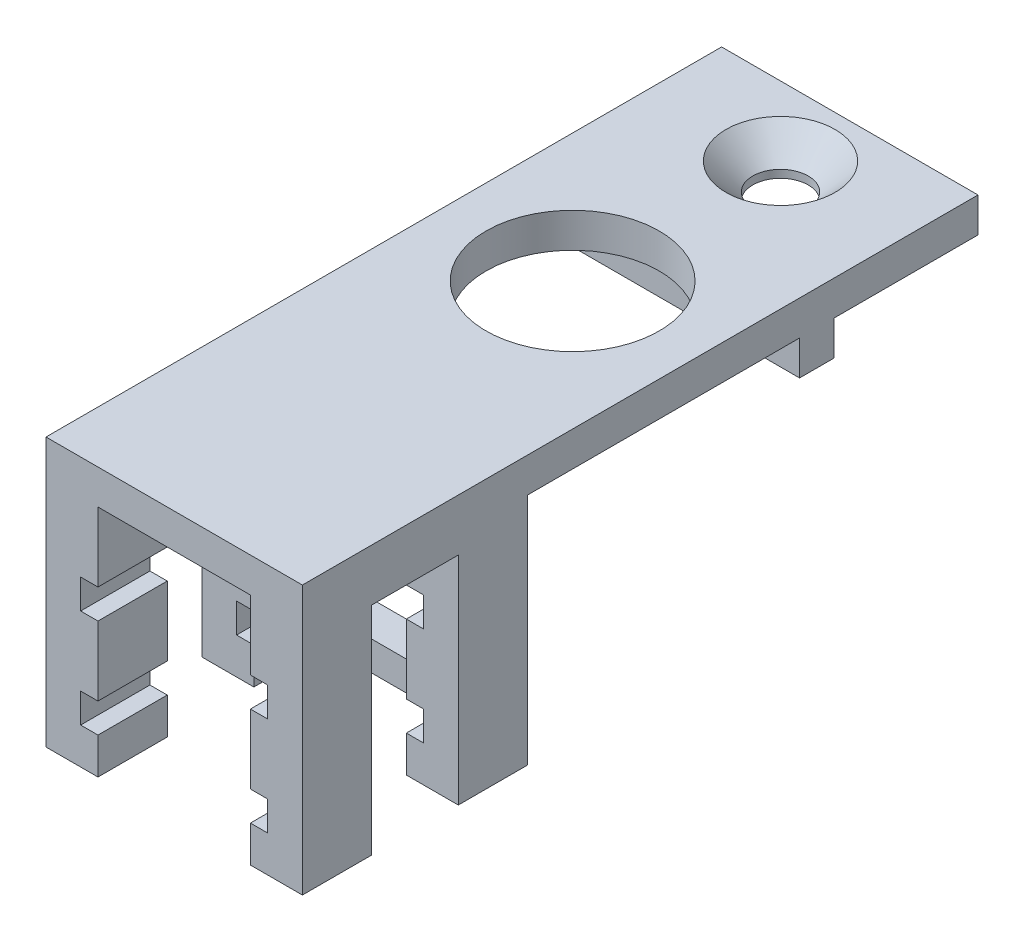
SolidWorks part; units mm, degrees
ref_plane "Front Plane" through (0, 0, 0) normal (0, 0, 1) x (1, 0, 0)
ref_plane "Top Plane" through (0, 0, 0) normal (0, 1, 0) x (1, 0, 0)
ref_plane "Right Plane" through (0, 0, 0) normal (1, 0, 0) x (0, 0, -1)
sketch "Sketch1" plane through (0, 0, 0) normal (0, 1, 0) x (1, 0, 0)
  line L5 (-6.5, -7.4) -> (6.5, -7.4)
  line L6 (-6.5, -7.4) -> (-6.5, 7.4)
  line L7 (-6.5, 7.4) -> (6.5, 7.4)
  line L8 (6.5, -7.4) -> (6.5, 7.4)
  line L9 (-6.5, -7.4) -> (6.5, 7.4) construction
  line L10 (-6.5, 7.4) -> (6.5, -7.4) construction
  point P0 (0, 0)
  dimension "D1" = 14.8
  dimension "D2" = 13
extrude "Boss-Extrude1" add sketch "Sketch1" along normal blind 15.5
sketch "Sketch2" plane through (6.5, 0, 0) normal (1, 0, 0) x (0, 0, -1)
  line L0 (-7.4, 0) -> (7.4, 0) construction
  line L1 (-5.4, 0) -> (5.4, 0)
  line L2 (-5.4, 0) -> (-5.4, 13.5)
  line L3 (-5.4, 13.5) -> (5.4, 13.5)
  line L4 (5.4, 0) -> (5.4, 13.5)
  line L5 (-7.4, 15.5) -> (7.4, 15.5) construction
  line L6 (-7.4, 15.5) -> (-7.4, 0) construction
  line L7 (7.4, 15.5) -> (7.4, 0) construction
  dimension "D1" = 2
  dimension "D2" = 2
  dimension "D3" = 2
extrude "Cut-Extrude1" cut sketch "Sketch2" against normal offset from surface (11 mm away) 2 up to face at (-6.5, 7.75, 0)
sketch "Sketch3" plane through (6.5, 0, 0) normal (1, 0, 0) x (0, 0, -1)
  line L0 (-7.4, 15.5) -> (-7.4, 0) construction
  line L1 (-7.4, 2.1) -> (-4.4, 2.1)
  line L2 (-7.4, 2.1) -> (-7.4, 0)
  line L3 (-7.4, 0) -> (-4.4, 0)
  line L4 (-4.4, 2.1) -> (-4.4, 0)
  line L7 (-7.4, 3.8) -> (-4.4, 3.8)
  line L8 (-7.4, 3.8) -> (-7.4, 7.8)
  line L9 (-7.4, 7.8) -> (-4.4, 7.8)
  line L10 (-4.4, 3.8) -> (-4.4, 7.8)
  line L11 (-7.4, 13.5) -> (-4.4, 13.5)
  line L12 (-7.4, 13.5) -> (-7.4, 9.5)
  line L13 (-7.4, 9.5) -> (-4.4, 9.5)
  line L14 (-4.4, 13.5) -> (-4.4, 9.5)
  line L15 (7.4, 15.5) -> (7.4, 0) construction
  line L16 (7.4, 0) -> (4.4, 0)
  line L17 (7.4, 0) -> (7.4, 2.1)
  line L18 (7.4, 2.1) -> (4.4, 2.1)
  line L19 (4.4, 0) -> (4.4, 2.1)
  line L20 (7.4, 3.8) -> (4.4, 3.8)
  line L21 (7.4, 3.8) -> (7.4, 7.8)
  line L22 (7.4, 7.8) -> (4.4, 7.8)
  line L23 (4.4, 3.8) -> (4.4, 7.8)
  line L24 (5.4, 13.5) -> (-5.4, 13.5) construction
  line L25 (7.4, 9.5) -> (4.4, 9.5)
  line L26 (7.4, 9.5) -> (7.4, 13.5)
  line L27 (7.4, 13.5) -> (4.4, 13.5)
  line L28 (4.4, 9.5) -> (4.4, 13.5)
  line L29 (-7.4, 0) -> (-5.4, 0) construction
  dimension "D1" = 4
  dimension "D2" = 1.7
  dimension "D3" = 4
  dimension "D4" = 1.7
  dimension "D5" = 3
  dimension "D6" = 3
  dimension "D7" = 1.7
extrude "Boss-Extrude2" add sketch "Sketch3" against normal blind 13
sketch "Sketch4" plane through (6.5, 0, 0) normal (1, 0, 0) x (0, 0, -1)
  line L1 (-4.4, 9.5) -> (4.4, 9.5)
  line L2 (-4.4, 9.5) -> (-4.4, 13.5)
  line L3 (-4.4, 13.5) -> (4.4, 13.5)
  line L4 (4.4, 9.5) -> (4.4, 13.5)
  line L5 (-4.4, 3.8) -> (4.4, 3.8)
  line L6 (-4.4, 3.8) -> (-4.4, 7.8)
  line L7 (-4.4, 7.8) -> (4.4, 7.8)
  line L8 (4.4, 3.8) -> (4.4, 7.8)
  line L9 (-4.4, 2.1) -> (4.4, 2.1)
  line L10 (-4.4, 2.1) -> (-4.4, 0)
  line L11 (-4.4, 0) -> (4.4, 0)
  line L12 (4.4, 2.1) -> (4.4, 0)
extrude "Cut-Extrude2" cut sketch "Sketch4" against normal through all
sketch "Sketch5" plane through (-6.5, 0, 0) normal (-1, 0, 0) x (0, 0, 1)
  line L0 (7.4, 15.5) -> (7.4, 0) construction
  line L1 (-7.4, 15.5) -> (7.4, 15.5)
  line L2 (-7.4, 15.5) -> (-7.4, 13.5)
  line L3 (-7.4, 13.5) -> (7.4, 13.5)
  line L4 (7.4, 15.5) -> (7.4, 13.5)
  dimension "D1" = 2
extrude "Boss-Extrude3" add sketch "Sketch5" along normal blind 26
sketch "Sketch7" plane through (0, 15.5, 0) normal (0, 1, 0) x (1, 0, 0)
  line L0 (-32.5, 0) -> (6.5, 0) construction
  line L1 (-32.5, -7.4) -> (-32.5, 7.4) construction
  line L2 (6.5, -7.4) -> (6.5, 7.4) construction
  line L3 (-28.5, 7.4) -> (-28.5, -7.4) construction
  line L4 (6.5, 7.4) -> (-32.5, 7.4) construction
  line L5 (-32.5, -7.4) -> (6.5, -7.4) construction
  point P12 (-28.5, 0)
  dimension "D1" = 4
hole_wizard "CSK for M3 Oval Head Machine Screw1" positions "Sketch7" profile "Sketch8" countersink size "M3" standard "ANSI Metric"
sketch "Sketch8" plane through (-28.5, 15.5, 0) normal (1, 0, 0) x (0, 0, 1)
  line L0 (0, 0) -> (0, 11.3614)
  line L1 (0, 11.3614) -> (1.6, 10.4)
  line L2 (1.6, 10.4) -> (1.6, 1.55)
  line L3 (1.6, 1.55) -> (3.15, 0)
  line L5 (3.15, 0) -> (0, 0)
  line L6 (-1.6, 1.55) -> (-3.15, 0) construction
  line L10 (0, 11.3614) -> (-1.6, 10.4) construction
  line L11 (0, -6.35) -> (0, 107.95) construction
  dimension "Hole Dia." = 3.2
  dimension "Hole Depth" = 10.4
  dimension "Near C'Sink Dia." = 6.3
  dimension "Near C'Sink Angle" = 90
  dimension "Drill Angle" = 118
sketch "Sketch6" plane through (0, 13.5, 0) normal (0, -1, 0) x (1, 0, 0)
  line L0 (-32.5, 7.4) -> (-6.5, 7.4) construction
  line L1 (-24.2, 7.4) -> (-22.2, 7.4)
  line L2 (-24.2, 7.4) -> (-24.2, -7.4)
  line L3 (-24.2, -7.4) -> (-22.2, -7.4)
  line L4 (-22.2, 7.4) -> (-22.2, -7.4)
  line L5 (-32.5, -7.4) -> (-6.5, -7.4) construction
  line L9 (-28.5, 0) -> (-28.5, 7.4) construction
  circle A0 centre (-28.5, 0) radius 1.15 construction
  dimension "D1" = 4.3
  dimension "D2" = 2
extrude "Boss-Extrude4" add sketch "Sketch6" along normal blind 2
sketch "Sketch9" plane through (0, 15.5, 0) normal (0, 1, 0) x (1, 0, 0)
  line L0 (-16.5, 7.4) -> (-16.5, -7.4) construction
  line L1 (6.5, 7.4) -> (-32.5, 7.4) construction
  line L2 (-32.5, -7.4) -> (6.5, -7.4) construction
  line L4 (6.5, -7.4) -> (6.5, 7.4) construction
  circle A0 centre (-16.5, 0) radius 5
  dimension "D1" = 10
  dimension "D2" = 23
extrude "Cut-Extrude3" cut sketch "Sketch9" against normal through all
sketch "Sketch10" plane through (0, 0, 7.4) normal (0, 0, 1) x (1, 0, 0)
  line L0 (-6.5, 0) -> (6.5, 0) construction
  line L1 (-2.5, 0) -> (2.5, 0)
  line L2 (-2.5, 0) -> (-2.5, 12.5)
  line L3 (-2.5, 12.5) -> (2.5, 12.5)
  line L4 (2.5, 0) -> (2.5, 12.5)
  line L5 (6.5, 15.5) -> (6.5, 0) construction
  line L6 (-6.5, 13.5) -> (-6.5, 0) construction
  line L7 (-32.5, 15.5) -> (6.5, 15.5) construction
  dimension "D1" = 4
  dimension "D2" = 4
  dimension "D3" = 3
extrude "Cut-Extrude4" cut sketch "Sketch10" against normal through all
move or copy body "Body-Move/Copy1" bodies to move or copy 109 copy no rotation origin (-13, 0, 0) rotation axis (0, -1, 0) rotation angle 90
